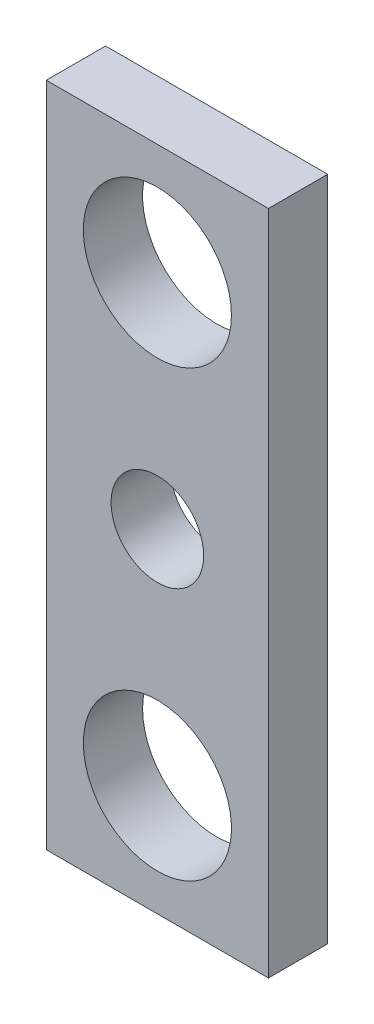
SolidWorks part; units mm, degrees
ref_plane "Front Plane" through (0, 0, 0) normal (0, 0, 1) x (1, 0, 0)
ref_plane "Top Plane" through (0, 0, 0) normal (0, 1, 0) x (1, 0, 0)
ref_plane "Right Plane" through (0, 0, 0) normal (1, 0, 0) x (0, 0, -1)
sketch "Sketch1" plane through (0, 0, 0) normal (0, 0, 1) x (1, 0, 0)
  line L0 (0, -180.975) -> (0, -219.075) construction
  line L1 (0, -200.025) -> (-9.525, -200.025) construction
  line L2 (-9.525, -228.6) -> (9.525, -228.6)
  line L3 (-9.525, -228.6) -> (-9.525, -171.45)
  line L4 (-9.525, -171.45) -> (9.525, -171.45)
  line L5 (9.525, -228.6) -> (9.525, -171.45)
  line L6 (-9.525, -228.6) -> (9.525, -171.45) construction
  line L7 (-9.525, -171.45) -> (9.525, -228.6) construction
  circle A0 centre (0, -180.975) radius 3.175 construction
  circle A1 centre (0, -200.025) radius 3.9687
  circle A2 centre (0, -180.975) radius 6.35
  circle A3 centre (0, -219.075) radius 3.175 construction
  circle A4 centre (0, -219.075) radius 6.35
  dimension "D1" = 6.35
  dimension "D2" = 7.9375
  dimension "D3" = 19.05
  dimension "D6" = 12.7
  dimension "D4" = 19.05
  dimension "D5" = 57.15
extrude "Boss-Extrude2" add sketch "Sketch1" along normal blind 5.08
